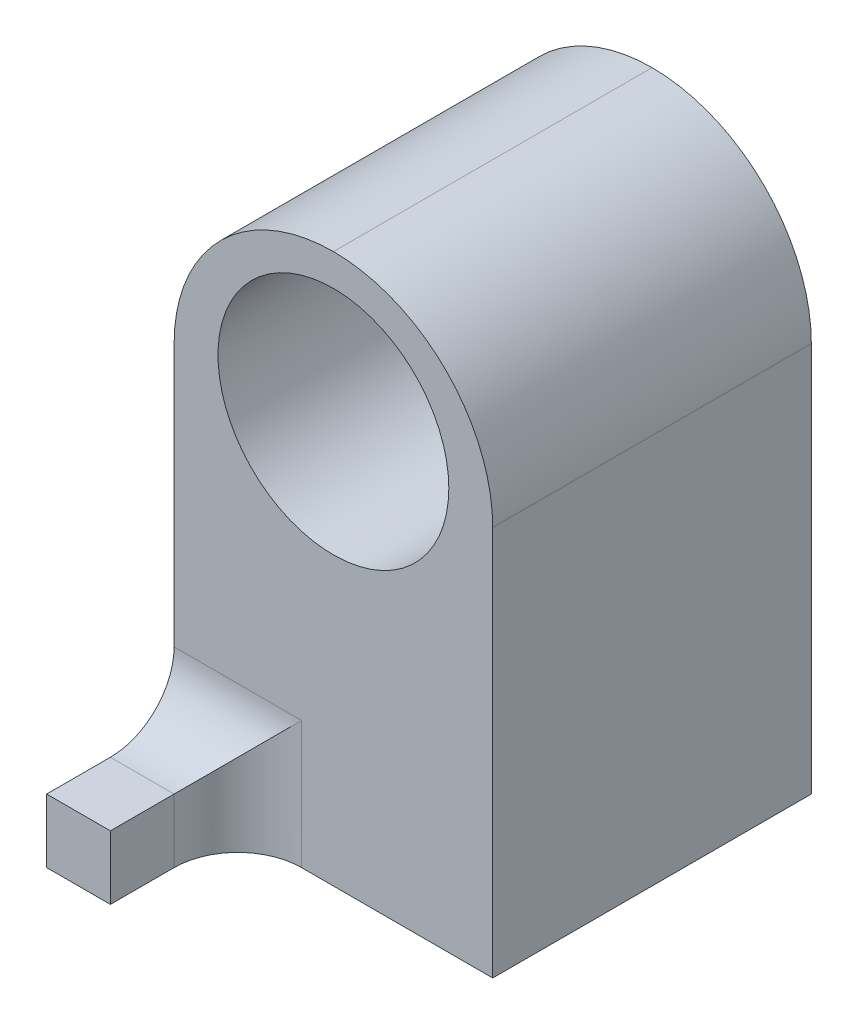
SolidWorks part; units mm, degrees
ref_plane "Front Plane" through (0, 0, 0) normal (0, 0, 1) x (1, 0, 0)
ref_plane "Top Plane" through (0, 0, 0) normal (0, 1, 0) x (1, 0, 0)
ref_plane "Right Plane" through (0, 0, 0) normal (1, 0, 0) x (0, 0, -1)
sketch "Sketch1" plane through (0, 0, 0) normal (0, 1, 0) x (1, 0, 0)
  line L1 (0, 0) -> (50.8, 0)
  line L2 (0, 0) -> (0, 50.8)
  line L3 (0, 50.8) -> (50.8, 50.8)
  line L4 (50.8, 0) -> (50.8, 50.8)
  line L5 (-6.35, -6.35) -> (57.15, -6.35)
  line L6 (-6.35, -6.35) -> (-6.35, 57.15)
  line L7 (-6.35, 57.15) -> (57.15, 57.15)
  line L8 (57.15, -6.35) -> (57.15, 57.15)
  dimension "D1" = 50.8
  dimension "D2" = 63.5
  dimension "D3" = 6.35
  dimension "D4" = 6.35
  dimension "D5" = 63.5
extrude "Boss-Extrude1" add sketch "Sketch1" along normal blind 50.8
sketch "Sketch2" plane through (0, 50.8, 0) normal (0, 1, 0) x (1, 0, 0)
  line L1 (-6.35, -6.35) -> (57.15, -6.35)
  line L2 (-6.35, -6.35) -> (-6.35, 57.15)
  line L3 (-6.35, 57.15) -> (57.15, 57.15)
  line L4 (57.15, -6.35) -> (57.15, 57.15)
extrude "Boss-Extrude3" add sketch "Sketch2" along normal blind 6.35
sketch "Sketch3" plane through (0, 57.15, 0) normal (0, 1, 0) x (1, 0, 0)
  line L1 (-6.35, -6.35) -> (57.15, -6.35)
  line L2 (-6.35, -6.35) -> (-6.35, 57.15)
  line L3 (-6.35, 57.15) -> (57.15, 57.15)
  line L4 (57.15, -6.35) -> (57.15, 57.15)
extrude "Boss-Extrude4" add sketch "Sketch3" along normal blind 52.3494
sketch "Sketch4" plane through (0, 0, 6.35) normal (0, 0, 1) x (1, 0, 0)
  line L0 (0, 50.8) -> (50.8, 50.8) construction
  line L1 (0, 50.8) -> (50.8, 50.8) construction
  line L2 (25.4, 50.8) -> (25.4, 109.4994) construction
  line L3 (-6.35, 109.4994) -> (57.15, 109.4994) construction
  circle A0 centre (25.4, 80.1497) radius 22.9997
  dimension "D1" = 45.9994
extrude "Cut-Extrude1" cut sketch "Sketch4" against normal through all
fillet "Fillet2" radius 31.75 2 edges at (-6.35, 109.4994, -25.4) (57.15, 109.4994, -25.4)
sketch "Sketch5" plane through (0, 0, 6.35) normal (0, 0, 1) x (1, 0, 0)
  line L1 (-6.35, 0) -> (6.35, 0)
  line L2 (-6.35, 0) -> (-6.35, 12.7)
  line L3 (-6.35, 12.7) -> (6.35, 12.7)
  line L4 (6.35, 0) -> (6.35, 12.7)
  dimension "D1" = 12.7
  dimension "D2" = 12.7
extrude "Boss-Extrude5" add sketch "Sketch5" along normal blind 25.4
fillet "Fillet3" radius 12.7 2 edges at (0, 12.7, 6.35) (6.35, 6.35, 6.35)
